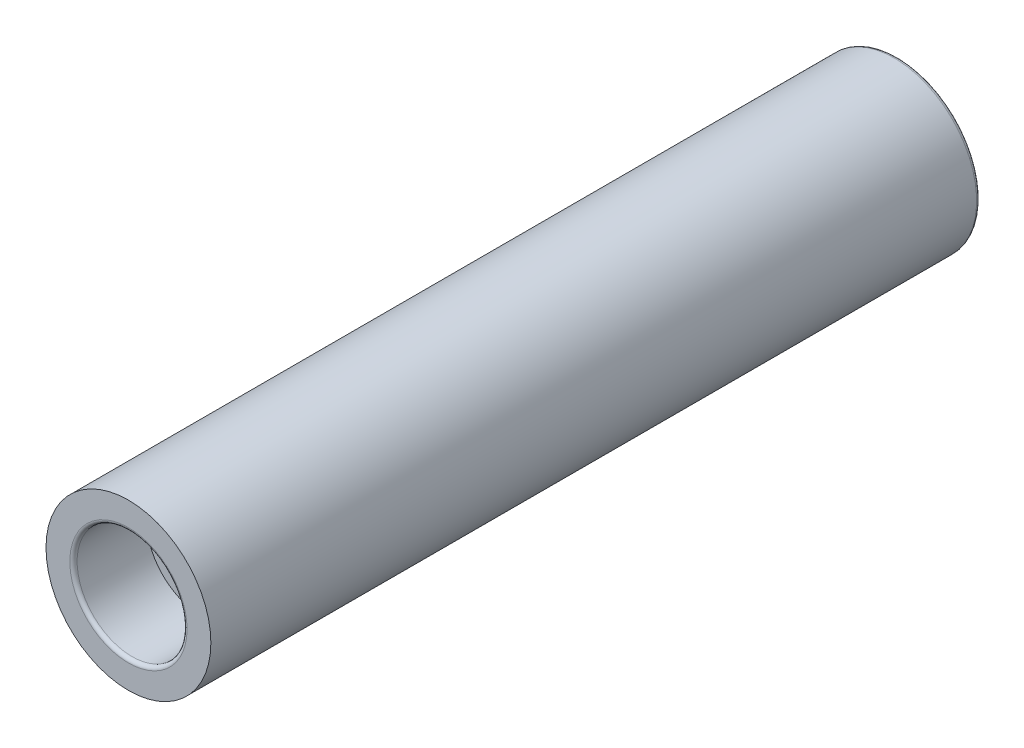
SolidWorks part; units mm, degrees
ref_plane "Front Plane" through (0, 0, 0) normal (0, 0, 1) x (1, 0, 0)
ref_plane "Top Plane" through (0, 0, 0) normal (0, 1, 0) x (1, 0, 0)
ref_plane "Right Plane" through (0, 0, 0) normal (1, 0, 0) x (0, 0, -1)
sketch "Sketch1" plane through (0, 0, 0) normal (0, 0, 1) x (1, 0, 0)
  circle A0 centre (0, 0) radius 4.5
  dimension "D1" = 9
extrude "Extrude-Thin1" add sketch "Sketch1" along normal blind 12 thin contours A0 thin type one direction reverse wall 3.5
sketch "Sketch11" plane through (0, 0, 12) normal (0, 0, 1) x (1, 0, 0)
  circle A0 centre (0, 0) radius 1.5
  dimension "D1" = 3
extrude "Extrude-Thin3" add sketch "Sketch11" along normal blind 5 thin thin type one direction wall 3
sketch "Sketch12" plane through (0, 0, 17) normal (0, 0, 1) x (1, 0, 0)
  circle A0 centre (0, 0) radius 3
  dimension "D1" = 6
extrude "Extrude-Thin4" add sketch "Sketch12" along normal blind 4 thin thin type one direction wall 1.5
thread "Thread1" pitch 0.5 method extrude profile "Thread Profile1" start angle 0, offset 0, length 5, pitch 0.5, diameter 3
ref_plane "Plane6" through (1.5, 0, 12) normal (0, -1, 0) x (1, 0, 0)
sketch "Thread Profile1" plane through (1.5, 0, 12) normal (0, -1, 0) x (1, 0, 0)
  line L0 (0, 0) -> (0, 0.5) construction
  line L11 (0, 0) -> (0, 0.4375)
  line L12 (0, 0.4375) -> (-0.2706, 0.2812)
  line L13 (-0.2706, 0.2812) -> (-0.2706, 0.1562)
  line L15 (-0.2706, 0.1562) -> (0, 0)
  line L17 (-0.2706, 0.2187) -> (0, 0.2187) construction
  point P2 (0, 0)
  dimension "Pitch" = 0.5
  dimension "Profile_Angle" = 60
  dimension "Profile_Land" = 0.125
  dimension "Profile_Height" = 0.2706
mirror "Mirror2" about plane through (0, 0, 0) normal (0, 0, 1) of "Extrude-Thin4", "Extrude-Thin3", "Thread1", "Extrude-Thin1"
fillet "Fillet1" radius 0.2 3 edges at (3, 0, 21) (4.5, 0, -21) (3, 0, -21)
